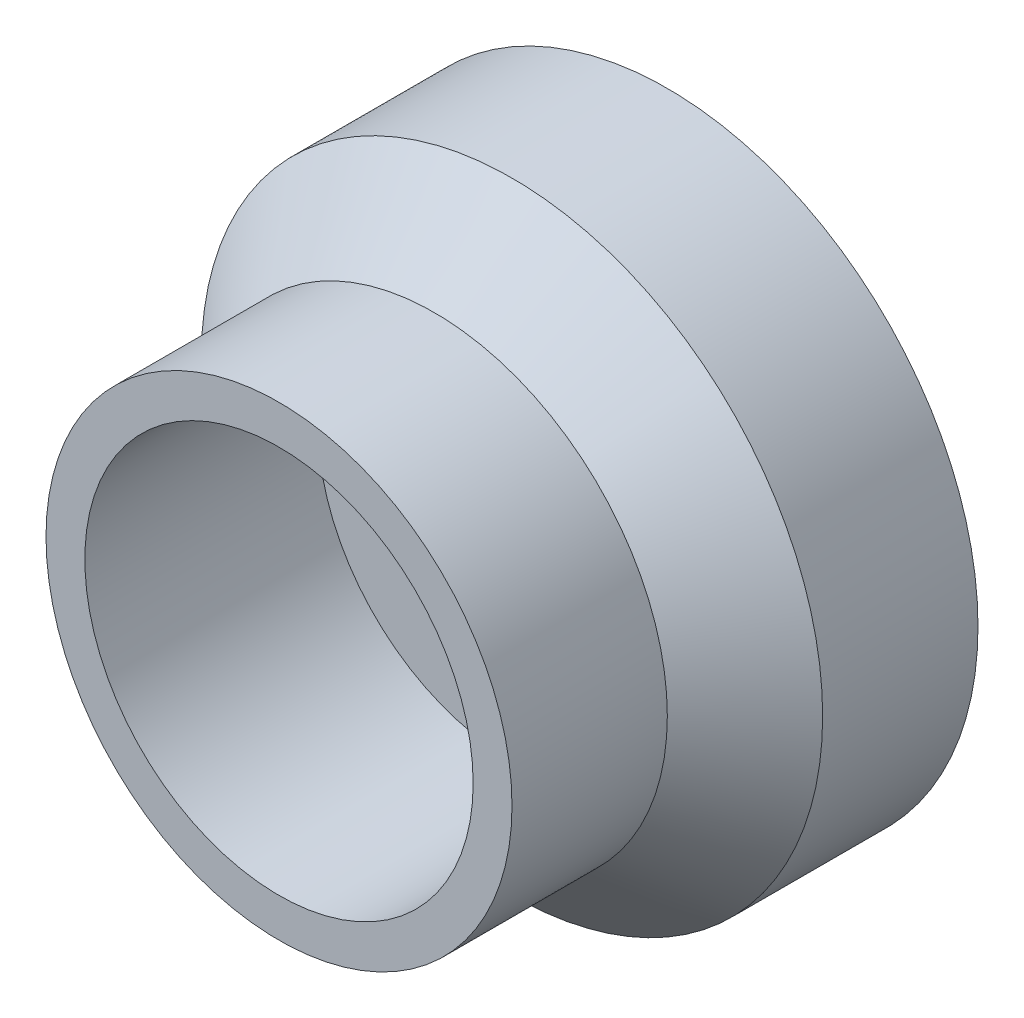
SolidWorks part; units mm, degrees
ref_plane "Front Plane" through (0, 0, 0) normal (0, 0, 1) x (1, 0, 0)
ref_plane "Top Plane" through (0, 0, 0) normal (0, 1, 0) x (1, 0, 0)
ref_plane "Right Plane" through (0, 0, 0) normal (1, 0, 0) x (0, 0, -1)
sketch "Sketch1" plane through (0, 0, 0) normal (0, 0, 1) x (1, 0, 0)
  circle A0 centre (0, 0) radius 12.5
  circle A1 centre (0, 0) radius 15
  circle A2 centre (0, 0) radius 20
  dimension "D1" = 25
  dimension "D2" = 30
  dimension "D3" = 40
extrude "Boss-Extrude1" add sketch "Sketch1" along normal blind 15 contours A1 A0 region at (-14.5757, 0, 0)
extrude "Boss-Extrude2" add sketch "Sketch1<3>" against normal blind 10 contours A0 | A1 A0 | A2 A1 region at (0, 0, 0) region at (-14.5757, 0, 0) region at (-19.4343, 0, 0)
sketch "Sketch1<3>" plane through (0, 0, 0) normal (0, 0, 1) x (1, 0, 0) same geometry as "Sketch1"
chamfer "Chamfer1" distance 5 angle 45 1 edges at (15, 0, 0)
